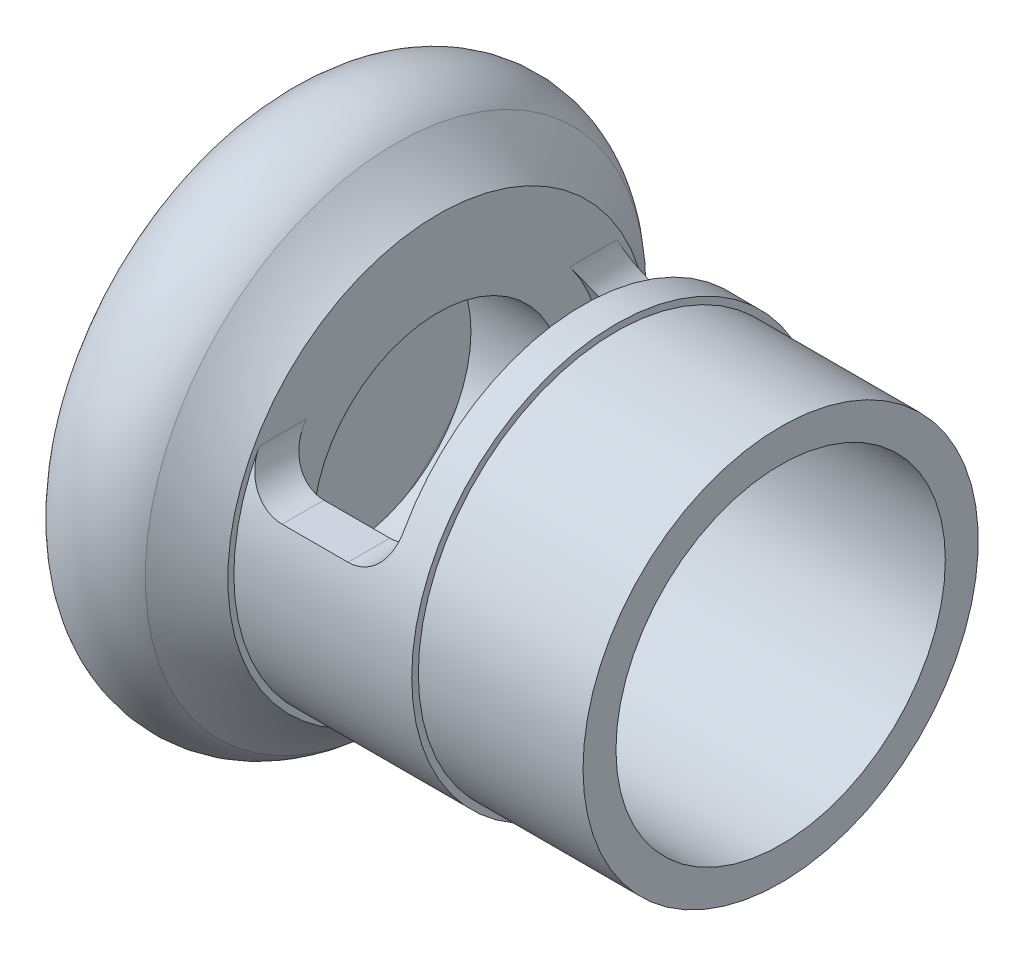
SolidWorks part; units mm, degrees
ref_plane "Front Plane" through (0, 0, 0) normal (0, 0, 1) x (1, 0, 0)
ref_plane "Top Plane" through (0, 0, 0) normal (0, 1, 0) x (1, 0, 0)
ref_plane "Right Plane" through (0, 0, 0) normal (1, 0, 0) x (0, 0, -1)
sketch "Sketch1" plane through (0, 0, 0) normal (0, 0, 1) x (1, 0, 0)
  line L0 (-49, 0) -> (49, 0) construction
  line L1 (49, 0) -> (49, 25) construction
  line L2 (49, 25) -> (19, 25)
  line L3 (19, 25) -> (19, 31)
  line L4 (19, 31) -> (24, 31)
  line L5 (24, 31) -> (24, 30)
  line L6 (24, 30) -> (49, 30)
  line L7 (49, 30) -> (49, 25)
revolve "Revolve1" add sketch "Sketch1" angle 360 about L0
sketch "Sketch3" plane through (19, 0, 0) normal (-1, 0, 0) x (0, 0, 1)
  circle A1 centre (0, 0) radius 31
  circle A2 centre (0, 0) radius 31
  circle A3 centre (0, 0) radius 25
  circle A4 centre (0, 0) radius 31
  circle M2 centre (0, 0) radius 25
  circle M3 centre (0, 0) radius 31
  dimension "D1" = 0
extrude "Boss-Extrude1" add sketch "Sketch3" along normal blind 22 contours M3 M2 region at (19, 0, -30.1232)
sketch "Sketch4" plane through (0, 0, 0) normal (0, 0, 1) x (1, 0, 0)
  line L0 (-3, 31) -> (19, 31)
  line L1 (24, 31) -> (-3, 31) construction
  line L2 (-3, 31) -> (-3, 15)
  line L3 (-3, 31) -> (-3, -31) construction
  line L4 (3, 9) -> (13, 9)
  line L5 (19, 15) -> (19, 31)
  arc A0 (13, 9) -> (19, 15) centre (13, 15) ccw
  arc A1 (3, 9) -> (-3, 15) centre (3, 15) cw
  point P13 (-3, 9)
  dimension "D1" = 6
extrude "Cut-Extrude1" cut sketch "Sketch4" against normal through all both and the other way through all
sketch "Sketch10" plane through (0, 0, 0) normal (0, 0, 1) x (1, 0, 0)
  line L0 (49, 30) -> (49, 10.2608) construction
  line L1 (49, -30) -> (49, 30) construction
  line L2 (49, 30) -> (49, -30) construction
  line L3 (49, 0) -> (-60.8461, 0) construction
  line L4 (-3, 19) -> (-3, 31.9128)
  line L5 (-28, 0) -> (-25, 0)
  line L7 (-17, 38.0042) -> (-17, 38)
  line L8 (-25, 30) -> (-25, 0)
  line L9 (-28, 30) -> (-28, 0)
  line L10 (-17, 22) -> (-17, 19)
  line L12 (-17, 19) -> (-3, 19)
  arc A0 (-17, 22) -> (-25, 30) centre (-17, 30) ccw
  arc A1 (-9.4502, 38) -> (-28, 30) centre (-17, 30) ccw
  arc A2 (-9.4502, 38) -> (-3, 31.9128) centre (22.324, 65.2077) ccw
  dimension "D1" = 8
revolve "Revolve2" add sketch "Sketch10" angle 360 about L3
